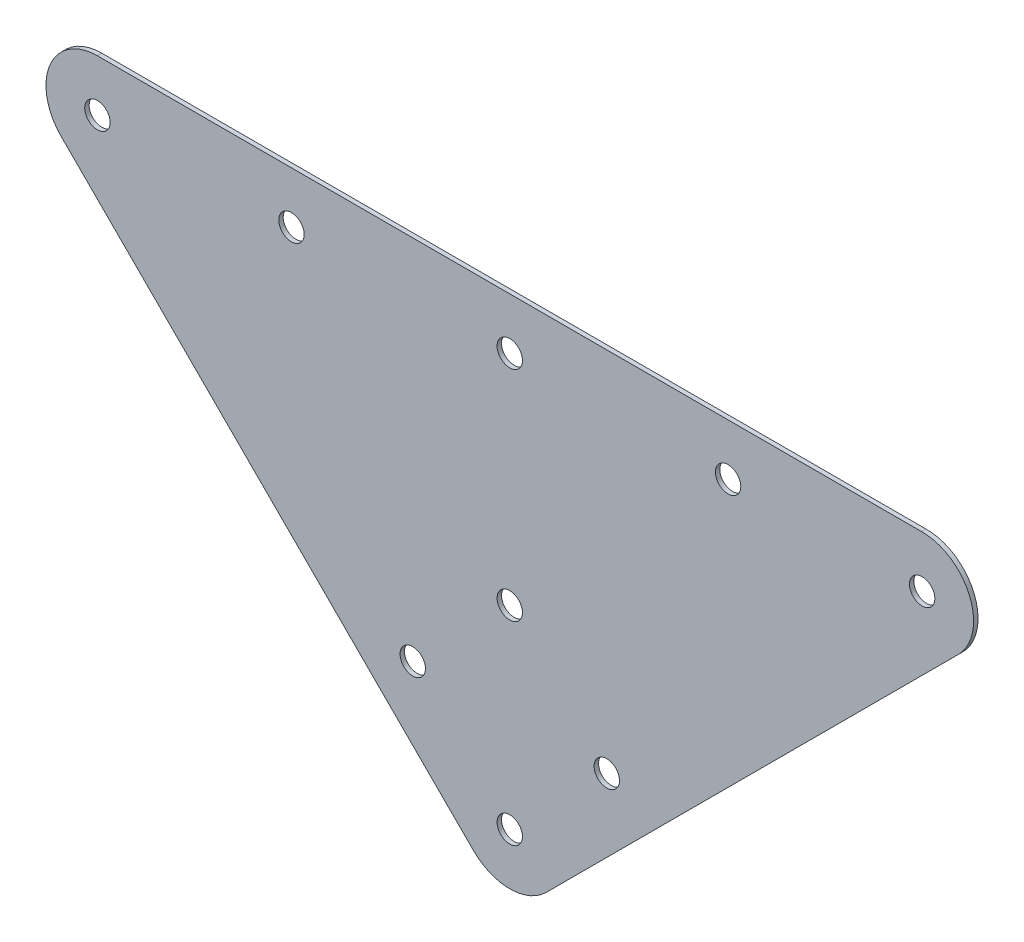
SolidWorks part; units mm, degrees
ref_plane "Front Plane" through (0, 0, 0) normal (0, 0, 1) x (1, 0, 0)
ref_plane "Top Plane" through (0, 0, 0) normal (0, 1, 0) x (1, 0, 0)
ref_plane "Right Plane" through (0, 0, 0) normal (1, 0, 0) x (0, 0, -1)
sketch "Sketch1" plane through (0, 0, 0) normal (0, 0, 1) x (1, 0, 0)
  line L0 (0, 0) -> (-46.2695, 0) construction
  line L1 (-198.6551, -198.6551) -> (-185.1847, -185.1847) construction
  line L2 (-198.6551, 0) -> (-198.6551, -198.6551) construction
  line L3 (-198.6551, -198.6551) -> (-212.1255, -185.1847) construction
  line L4 (-198.6551, -19.05) -> (-279.4774, -19.05) construction
  line L5 (-438.6608, -38.1) -> (83.6453, -38.1) construction
  line L6 (-198.6551, -19.05) -> (-117.8328, -19.05) construction
  line L7 (-279.4774, -19.05) -> (-351.3195, -19.05) construction
  line L8 (-117.8328, -19.05) -> (-45.9908, -19.05) construction
  line L9 (-198.6551, -198.6551) -> (-198.6551, -171.7144) construction
  line L10 (-198.6551, -171.7144) -> (-162.7341, -135.7933) construction
  line L11 (-198.6551, -171.7144) -> (-234.5761, -135.7933) construction
  line L12 (-234.5761, -135.7933) -> (-198.6551, -99.8723) construction
  line L13 (-162.7341, -135.7933) -> (-198.6551, -99.8723) construction
  line L14 (-351.3195, -19.05) -> (-234.5761, -135.7933) construction
  line L15 (-198.6551, -99.8723) -> (-117.8328, -19.05) construction
  line L16 (-162.7341, -135.7933) -> (-45.9908, -19.05) construction
  line L17 (-198.6551, 0) -> (-198.6551, 114.021) construction
  line L18 (-32.7175, -32.7175) -> (0, 0) construction
  line L19 (-46.2695, 0) -> (-351.3195, 0)
  line L20 (-351.3195, 0) -> (-397.3102, 0) construction
  line L21 (-364.7899, -32.5204) -> (-397.3102, 0) construction
  line L22 (-212.1255, -185.1847) -> (-364.7899, -32.5204)
  line L23 (-185.1847, -185.1847) -> (-32.7175, -32.7175)
  circle A0 centre (-198.6551, -19.05) radius 4.699
  circle A1 centre (-279.4774, -19.05) radius 4.699
  circle A2 centre (-117.8328, -19.05) radius 4.699
  circle A3 centre (-351.3195, -19.05) radius 4.699
  circle A4 centre (-45.9908, -19.05) radius 4.699
  circle A5 centre (-351.3195, -19.05) radius 19.05 construction
  circle A6 centre (-45.9908, -19.05) radius 19.05 construction
  circle A7 centre (-198.6551, -171.7144) radius 4.699
  circle A8 centre (-198.6551, -171.7144) radius 19.05 construction
  circle A9 centre (-162.7341, -135.7933) radius 4.699
  circle A10 centre (-162.7341, -135.7933) radius 19.05 construction
  circle A11 centre (-234.5761, -135.7933) radius 4.699
  circle A12 centre (-198.6551, -99.8723) radius 4.699
  arc A13 (-364.7899, -32.5204) -> (-351.3195, 0) centre (-351.3195, -19.05) cw
  arc A14 (-46.2695, 0) -> (-32.7175, -32.7175) centre (-45.9908, -19.05) cw
  arc A15 (-212.1255, -185.1847) -> (-185.1847, -185.1847) centre (-198.6551, -171.7144) ccw
  point P36 (0, 0)
  point P37 (0, 0)
  point P38 (0, 0)
  point P39 (15.5424, -26.8931)
  point P40 (-364.7899, -32.5204)
  point P41 (-419.5583, 11.3899)
  point P42 (-248.2392, -175.7802)
  point P43 (0, 0)
  point P44 (0, 0)
  dimension "D2" = 9.398
  dimension "D3" = 88.9
  dimension "D4" = 38.1
  dimension "D5" = 165.1
  dimension "D1" = 397.3102
  dimension "D6" = 45
extrude "Boss-Extrude3" add sketch "Sketch1" along normal blind 1.6418 contours A4 | A2 | A0 | A1 | A9 | A7 | A11 | A12 | A3 | L23 A14 L19 A13 L22 A15
